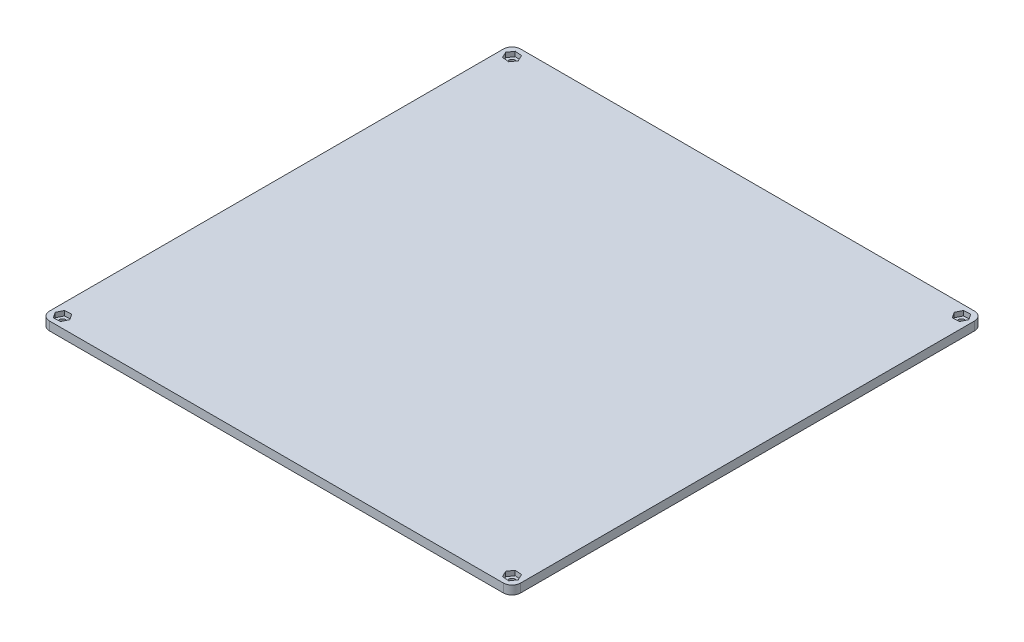
SolidWorks part; units mm, degrees
ref_plane "前视基准面" through (0, 0, 0) normal (0, 0, 1) x (1, 0, 0)
ref_plane "上视基准面" through (0, 0, 0) normal (0, 1, 0) x (1, 0, 0)
ref_plane "右视基准面" through (0, 0, 0) normal (1, 0, 0) x (0, 0, -1)
sketch "草图1" plane through (0, 0, 0) normal (0, 1, 0) x (1, 0, 0)
  line L1 (109, 109) -> (-109, 109)
  line L2 (109, 109) -> (109, -109)
  line L3 (109, -109) -> (-109, -109)
  line L4 (-109, 109) -> (-109, -109)
  line L5 (109, 109) -> (-109, -109) construction
  line L6 (109, -109) -> (-109, 109) construction
  point P0 (0, 0)
  dimension "D1" = 218
  dimension "D2" = 218
extrude "凸台-拉伸1" add sketch "草图1" along normal blind 4
fillet "圆角1" radius 4 4 edges at (-109, 2, -109) (109, 2, -109) (109, 2, 109) (-109, 2, 109)
sketch "草图2" plane through (0, 4, 0) normal (0, 1, 0) x (1, 0, 0)
  line L0 (105, 109) -> (-105, 109) construction
  line L1 (105.3752, 106.8622) -> (102.2088, 106.622)
  line L2 (102.2088, 106.622) -> (100.8337, 103.7598)
  line L3 (100.8337, 103.7598) -> (102.6248, 101.1378)
  line L4 (102.6248, 101.1378) -> (105.7912, 101.378)
  line L5 (105.7912, 101.378) -> (107.1663, 104.2402)
  line L6 (107.1663, 104.2402) -> (105.3752, 106.8622)
  line L7 (109, -105) -> (109, 105) construction
  line L8 (-105, -109) -> (105, -109) construction
  line L9 (-109, 105) -> (-109, -105) construction
  line L10 (107.1663, -104.2402) -> (105.3752, -106.8622)
  line L11 (105.3752, -106.8622) -> (102.2088, -106.622)
  line L12 (102.2088, -106.622) -> (100.8337, -103.7598)
  line L13 (100.8337, -103.7598) -> (102.6248, -101.1378)
  line L14 (102.6248, -101.1378) -> (105.7912, -101.378)
  line L15 (-107.1663, -104.2402) -> (-105.3752, -106.8622)
  line L16 (-105.3752, -106.8622) -> (-102.2088, -106.622)
  line L17 (-102.2088, -106.622) -> (-100.8337, -103.7598)
  line L18 (-100.8337, -103.7598) -> (-102.6248, -101.1378)
  line L19 (-102.6248, -101.1378) -> (-105.7912, -101.378)
  line L20 (-105.7912, 101.378) -> (-107.1663, 104.2402)
  line L21 (-107.1663, 104.2402) -> (-105.3752, 106.8622)
  line L22 (-105.3752, 106.8622) -> (-102.2088, 106.622)
  line L23 (-102.2088, 106.622) -> (-100.8337, 103.7598)
  line L24 (-100.8337, 103.7598) -> (-102.6248, 101.1378)
  line L25 (-102.6248, 101.1378) -> (-105.7912, 101.378)
  line L26 (107.1663, -104.2402) -> (105.7912, -101.378)
  line L27 (-107.1663, -104.2402) -> (-105.7912, -101.378)
  circle A0 centre (104, 104) radius 2.75 construction
  circle A1 centre (104, 104) radius 1.5
  circle A2 centre (104, -104) radius 1.5
  circle A3 centre (-104, -104) radius 1.5
  circle A4 centre (-104, 104) radius 1.5
  point P1 (101.7292, 102.4488)
  dimension "D4" = 5
  dimension "D6" = 5
  dimension "D8" = 5
  dimension "D1" = 5.5
  dimension "D2" = 5
  dimension "D3" = 5
  dimension "D5" = 5
  dimension "D7" = 5
  dimension "D9" = 5
extrude "切除-拉伸3" cut sketch "草图2" against normal blind 2.2
extrude "切除-拉伸4" cut sketch "草图2<3>" against normal through all contours A2 | A3 | A4 | A1 region at (104, 4, -104) region at (104, 4, 104) region at (-104, 4, 104) region at (-104, 4, -104)
sketch "草图2<3>" plane through (0, 4, 0) normal (0, 1, 0) x (1, 0, 0) same geometry as "草图2"
